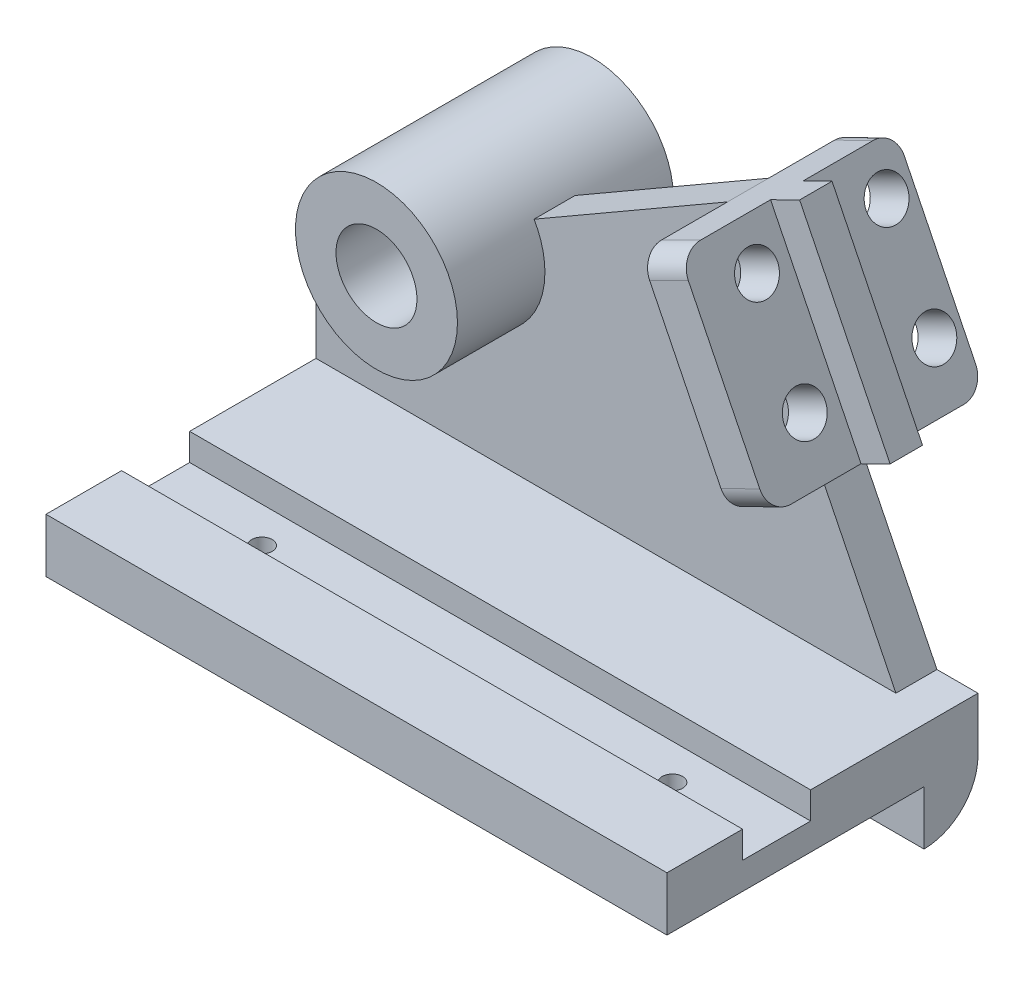
SolidWorks part; units mm, degrees
ref_plane "Front Plane" through (0, 0, 0) normal (0, 0, 1) x (1, 0, 0)
ref_plane "Top Plane" through (0, 0, 0) normal (0, 1, 0) x (1, 0, 0)
ref_plane "Right Plane" through (0, 0, 0) normal (1, 0, 0) x (0, 0, -1)
sketch "Sketch1" plane through (0, 0, 0) normal (1, 0, 0) x (0, 0, -1)
  line L0 (0, 5) -> (0, 10)
  line L1 (0, 10) -> (7, 10)
  line L2 (7, 10) -> (7, 7.5)
  line L3 (7, 7.5) -> (13.3, 7.5)
  line L4 (13.3, 7.5) -> (13.3, 10)
  line L5 (13.3, 10) -> (28.8, 10)
  line L6 (28.8, 10) -> (28.8, 0)
  line L7 (28.8, 0) -> (23.8, 0)
  line L8 (23.8, 0) -> (23.8, 5)
  line L9 (23.8, 5) -> (0, 5)
  dimension "D1" = 5
  dimension "D2" = 10
  dimension "D3" = 5
  dimension "D4" = 6.3
  dimension "D5" = 28.8
  dimension "D6" = 7
  dimension "D7" = 2.5
extrude "Boss-Extrude1" add sketch "Sketch1" along normal blind 57.5
fillet "Fillet1" radius 5 1 edges at (28.75, 0, -28.8)
sketch "Sketch2" plane through (0, 0, -28.8) normal (0, 0, -1) x (-1, 0, 0)
  line L0 (-57.5, 10) -> (0, 10) construction
  line L1 (-53.7, 10) -> (0, 10)
  line L2 (0, 10) -> (0, 19.6)
  line L3 (0, 19.6) -> (-38.1051, 41.6)
  line L4 (-38.1051, 41.6) -> (-53.7, 10)
  line L5 (-57.5, 10) -> (-57.5, 5) construction
  line L6 (-57.5, 0) -> (0, 0) construction
  dimension "D1" = 3.8
  dimension "D2" = 19.6
  dimension "D3" = 30
  dimension "D4" = 44
extrude "Boss-Extrude2" add sketch "Sketch2" against normal blind 3.8
sketch "Sketch3" plane through (0, 0, -25) normal (0, 0, 1) x (1, 0, 0)
  line L0 (0, 19.6) -> (38.1051, 41.6) construction
  circle A0 centre (13.7, 27.5097) radius 7.5
  dimension "D1" = 15
  dimension "D2" = 13.7
extrude "Boss-Extrude3" add sketch "Sketch3" along normal blind 8.1 and the other way blind 11.9
hole_wizard "Hole1" positions "Sketch4" profile "Sketch5" legacy end condition up to next
sketch "Sketch4" plane through (0, 0, -16.9) normal (0, 0, 1) x (1, 0, 0)
  point P0 (13.7, 27.5097)
sketch "Sketch5" plane through (13.7, 27.5097, -16.9) normal (1, 0, 0) x (0, -1, 0)
  line L0 (0, 0) -> (0, 20)
  line L1 (0, 20) -> (3.75, 20)
  line L2 (3.75, 20) -> (3.75, 0)
  line L3 (3.75, 0) -> (0, 0)
  line L4 (0, 110) -> (0, -10) construction
  dimension "Diameter" = 7.5
  dimension "Depth" = 20
sketch "Sketch6" plane through (0, 0, -25) normal (0, 0, 1) x (1, 0, 0)
  line L1 (38.1051, 41.6) -> (41.6921, 43.3702)
  line L2 (41.6921, 43.3702) -> (50.0734, 26.3871)
  line L3 (50.0734, 26.3871) -> (46.4864, 24.6169)
  line L4 (38.1051, 41.6) -> (53.7, 10) construction
  line L7 (46.4864, 24.6169) -> (38.1051, 41.6)
  dimension "D1" = 4
  dimension "D2" = 16.3
extrude "Boss-Extrude4" add sketch "Sketch6" along normal blind 8.1 and the other way blind 11.9
sketch "Sketch7" plane through (50.7383, 25.0398, 0) normal (0.8967, 0.4426, 0) x (0, 0, -1)
  line L0 (26.9, 1.5025) -> (26.9, 30.202) construction
  line L1 (36.9, 1.5025) -> (16.9, 1.5025) construction
  line L3 (25.4, 20.4411) -> (28.4, 20.4411)
  line L4 (25.4, 20.4411) -> (25.4, 1.5025)
  line L5 (25.4, 1.5025) -> (28.4, 1.5025)
  line L6 (28.4, 20.4411) -> (28.4, 1.5025)
  line L7 (25.4, 20.4411) -> (28.4, 1.5025) construction
  line L8 (25.4, 1.5025) -> (28.4, 20.4411) construction
  line L10 (36.9, 20.4411) -> (16.9, 20.4411) construction
  point P5 (26.9, 10.9718)
  point P13 (4.4899, 23.7619)
  dimension "D1" = 3
extrude "Boss-Extrude5" add sketch "Sketch7" along normal blind 3
hole_wizard "Hole2" positions "Sketch8" profile "Sketch9" legacy end condition up to next
sketch "Sketch8" plane through (50.7383, 25.0398, 0) normal (0.8967, 0.4426, 0) x (0, 0, -1)
  line L0 (36.9, 1.5025) -> (36.9, 20.4411) construction
  line L1 (36.9, 1.5025) -> (28.4, 1.5025) construction
  point P0 (34.4, 6.5025)
  point P2 (22.4, 6.5025)
  point P4 (22.4, 16.5025)
  point P6 (34.4, 16.5025)
  point P13 (0, 0)
  point P14 (0, 0)
  point P15 (22.4, 6.5025)
  point P16 (0, 0)
  dimension "D1" = 12
  dimension "D2" = 10
  dimension "D3" = 2.5
  dimension "D4" = 5
sketch "Sketch9" plane through (47.8606, 30.8708, -34.4) normal (0, 0, 1) x (-0.4426, 0.8967, 0)
  line L0 (0, 0) -> (0, 4)
  line L1 (0, 4) -> (1.9, 4)
  line L2 (1.9, 4) -> (1.9, 0)
  line L3 (1.9, 0) -> (0, 0)
  line L4 (0, 110) -> (0, -10) construction
  dimension "Diameter" = 3.8
  dimension "Depth" = 4
fillet "Fillet2" radius 2 4 edges at (39.8986, 42.4851, -36.9) (39.8986, 42.4851, -16.9) (48.2799, 25.502, -16.9) (48.2799, 25.502, -36.9)
hole_wizard "Hole3" positions "Sketch10" profile "Sketch11" legacy end condition up to next
sketch "Sketch10" plane through (0, 7.5, 0) normal (0, 1, 0) x (1, 0, 0)
  line L0 (0, 13.3) -> (0, 7) construction
  line L1 (57.5, 0) -> (0, 0) construction
  point P0 (10, 10)
  dimension "D1" = 10
  dimension "D2" = 10
sketch "Sketch11" plane through (10, 7.5, -10) normal (1, 0, 0) x (0, 0, 1)
  line L0 (0, 0) -> (0, 2.5)
  line L1 (0, 2.5) -> (0.95, 2.5)
  line L2 (0.95, 2.5) -> (0.95, 0)
  line L3 (0.95, 0) -> (0, 0)
  line L4 (0, 110) -> (0, -10) construction
  dimension "Diameter" = 1.9
  dimension "Depth" = 2.5
pattern_linear "LPattern1" count 2 spacing 38 along (1, 0, 0) of "Hole3"
